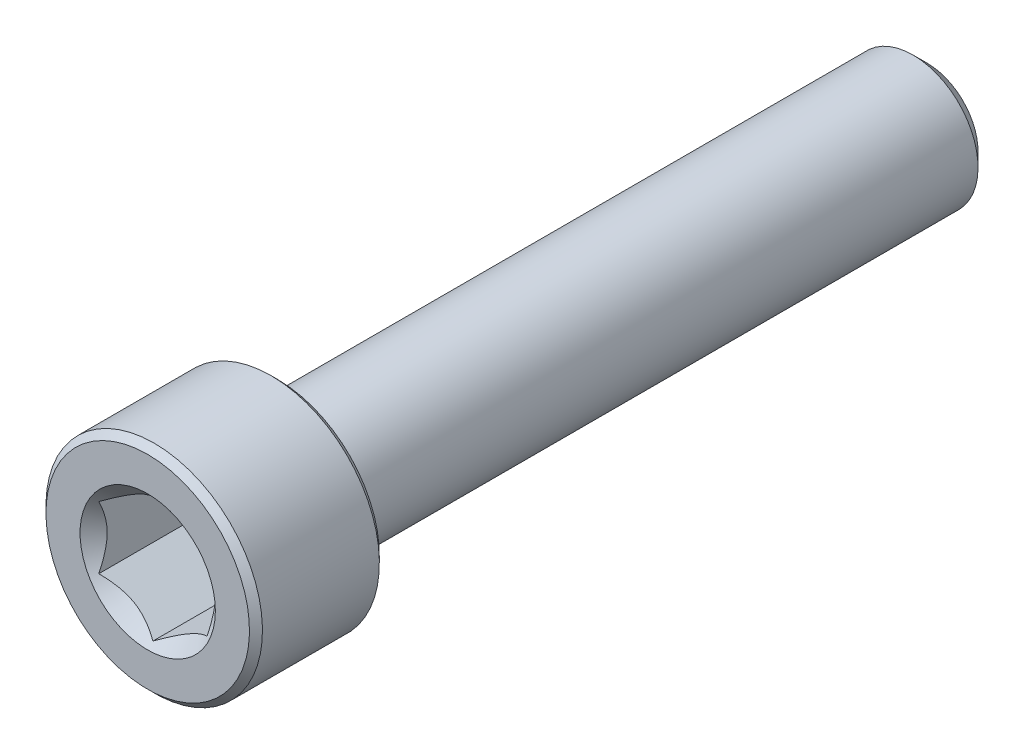
SolidWorks part; units mm, degrees
ref_plane "Front Plane" through (0, 0, 0) normal (0, 0, 1) x (1, 0, 0)
ref_plane "Top Plane" through (0, 0, 0) normal (0, 1, 0) x (1, 0, 0)
ref_plane "Right Plane" through (0, 0, 0) normal (1, 0, 0) x (0, 0, -1)
sketch "Sketch1" plane through (0, 0, 0) normal (1, 0, 0) x (0, 0, -1)
  line L0 (-18, 0) -> (18, 0) construction
  line L1 (18, 0) -> (18, 2.3505) construction
  line L2 (18, 2.3505) -> (17.3505, 3) construction
  line L3 (17.3505, 3) -> (17.25, 3) construction
  line L4 (17.25, 3) -> (-12, 3) construction
  line L5 (-12, 3) -> (-12, 5) construction
  line L6 (-12, 5) -> (-18, 5) construction
  line L7 (-18, 5) -> (-18, 0) construction
  line L8 (18, 2.3505) -> (18, 3) construction
  line L9 (17.9375, 3.1083) -> (18.4375, 2.2422) construction
  line L10 (18.4375, 2.2422) -> (18.9375, 3.1083) construction
  line L11 (18.9375, 3.1083) -> (17.9375, 3.1083) construction
  line L12 (18.4375, 3.1083) -> (18.4375, 3) construction
  line L13 (18.4375, 2.2422) -> (18.4375, 2.3505) construction
  line L14 (18.375, 2.3505) -> (18.5, 2.3505) construction
  line L15 (18, 3) -> (18.875, 3) construction
  line L16 (17.9687, 3.0541) -> (18.9063, 3.0541) construction
  line L17 (18, 0) -> (18, -3) construction
  line L18 (-12.3, 5) -> (-12, 4.7) construction
  line L19 (-17.7, 5) -> (-18, 4.7) construction
  line L20 (-12, 3) -> (-12, 0) construction
  line L21 (-12, 1.5) -> (-2, 1.5) construction
  line L22 (-2, 1.5) -> (8, 1.5) construction
  line L23 (8, 1.5) -> (18, 1.5) construction
  line L24 (-2, 1.5) -> (-2, 3) construction
  line L25 (-2, 3) -> (-2, 5) construction
  line L26 (8, 1.5) -> (8, 5) construction
  point P0 (-18, 2.5)
  point P3 (15.5, 3)
  point P4 (0, 0)
  point P18 (8, 3)
  point P22 (18.4375, 2.3505)
  point P24 (17.25, 3)
  point P25 (18.4375, 3)
  point P28 (18.4375, 3.0541)
  point P29 (15.5, -3)
  point P30 (-2, 3)
  point P31 (-15, 5)
  point P37 (-13.05, 5)
  point P38 (-17.55, 5)
  point P45 (-2, 1.5)
  point P46 (8, 1.5)
  dimension "D2" = 0.125
  dimension "D7" = 0.3
  dimension "D8" = 0.3
  dimension "D9" = 0.3
  dimension "D10" = 0.15
  dimension "D11" = 0.75
  dimension "Drive Size" = 5
  dimension "Head Diameter" = 10
  dimension "Head Height" = 6
  dimension "Thread Pitch" = 1
  dimension "Thread Size" = 6
  dimension "Length" = 30
  dimension "D12" = 0.75
  dimension "D4" = 2.5
  dimension "D3" = 45
sketch "Sketch2" plane through (0, 0, 0) normal (1, 0, 0) x (0, 0, -1)
  line L0 (-18, 0) -> (-18, 4.7)
  line L1 (-17.7, 5) -> (-12.3, 5)
  line L2 (-12, 4.7) -> (-12, 3.3)
  line L4 (17.3505, 3) -> (18, 2.3505)
  line L5 (18, 2.3505) -> (18, 0)
  line L6 (-12, 5) -> (-18, 5) construction
  line L7 (18, 0) -> (-18, 0)
  line L8 (-17.7, 5) -> (-18, 4.7) construction
  line L10 (-17.7, 5) -> (-18, 4.7)
  line L14 (-12.3, 5) -> (-12, 4.7) construction
  line L16 (-12.3, 5) -> (-12, 4.7)
  line L17 (-12, 3) -> (-12, 5) construction
  line L19 (-11.7, 3) -> (17.3505, 3)
  line L20 (17.25, 3) -> (-12, 3) construction
  arc A1 (-12, 3.3) -> (-11.7, 3) centre (-11.7, 3.3) ccw
  dimension "D3" = 0.3
revolve "Revolve1" add sketch "Sketch2" angle 360 about L7
sketch "Sketch3" plane through (0, 0, 18) normal (0, 0, 1) x (1, 0, 0)
  line L1 (2.5, -1.4434) -> (2.5, 1.4434)
  line L2 (2.5, 1.4434) -> (0, 2.8868)
  line L3 (0, 2.8868) -> (-2.5, 1.4434)
  line L4 (-2.5, 1.4434) -> (-2.5, -1.4434)
  line L5 (-2.5, -1.4434) -> (0, -2.8868)
  line L6 (0, -2.8868) -> (2.5, -1.4434)
  circle A0 centre (0, 0) radius 2.5 construction
  circle A1 centre (0, 0) radius 5 construction
  circle A2 centre (0, 0) radius 5 construction
  circle A3 centre (0, 0) radius 2.8868 construction
  point P13 (0, 0)
extrude "Cut-Extrude1" cut sketch "Sketch3" against normal offset from surface (5 mm away) 1 up to face at (0, 4.7, 12)
sketch "Sketch4" plane through (0, 0, 18) normal (0, 0, 1) x (1, 0, 0)
  circle A0 centre (0, 0) radius 3.125
  dimension "D1" = 6.25
extrude "Cut-Extrude2" cut sketch "Sketch4" against normal up to vertex (3 mm away) draft 45 up to point (0, 5, 15)
sketch "Sketch11" plane through (0, 0, 0) normal (1, 0, 0) x (0, 0, -1)
  line L0 (-18, 0) -> (18, 0) construction
  line L1 (-18, 0) -> (18, 0) construction
  line L2 (-6.375, 0) -> (-6.375, 3) construction
  line L3 (17.25, 3) -> (-12, 3) construction
  line L4 (12.375, 0) -> (12.375, 3) construction
  line L6 (18, 2.3505) -> (18, 3) construction
  point P2 (-6.375, 0)
  point P3 (12.375, 0)
  dimension "D1" = 5.625
  dimension "D2" = 5.625
sketch "Sketch6" [suppressed] plane through (0, 0, -18) normal (0, 0, -1) x (-1, 0, 0)
  circle A0 centre (0, 0) radius 3
curve "Helix/Spiral1" [suppressed] pitch 1 height 31 turns 31
sketch "Sketch10" [suppressed] plane through (0, 0, 0) normal (1, 0, 0) x (0, 0, -1)
  line L0 (-11.7, -5) -> (-11.7, 5)
  line L5 (-18, 0) -> (18, 0) construction
  line L6 (-11.7, 3) -> (-11.7, -3) construction
  point P3 (-11.7, 0)
split "Split1" [suppressed] bodies to split 106
sketch "Sketch7" [suppressed] plane through (0, 0, 0) normal (1, 0, 0) x (0, 0, -1)
  line L0 (17.9687, 3.0541) -> (18.9063, 3.0541)
  line L1 (18.9063, 3.0541) -> (18.5, 2.3505)
  line L2 (18.5, 2.3505) -> (18.375, 2.3505)
  line L3 (18.375, 2.3505) -> (17.9687, 3.0541)
sweep "Cut-Sweep1" [suppressed] cut profiles "Sketch7" path "Helix/Spiral1"
sketch "Sketch8" [suppressed] plane through (0, 0, 0) normal (1, 0, 0) x (0, 0, -1)
  line L0 (-12, 0) -> (-12, 3)
  line L1 (-11.7, -3) -> (-11.7, 3) construction
  line L2 (-12, 3) -> (-11.7, 3)
  line L4 (-11.7, 3) -> (-9.9679, 0)
  line L5 (-9.9679, 0) -> (-12, 0)
  line L6 (17.25, 3) -> (-12, 3) construction
  line L7 (-18, 0) -> (18, 0) construction
  dimension "D1" = 60
revolve "Revolve2" [suppressed] add sketch "Sketch8" angle 360 about L5
ref_plane "Plane1" [suppressed] through (0, 0, 18) normal (0, 0, 1) x (1, 0, 0)
sketch "Sketch12" [suppressed] plane through (0, 0, 18) normal (0, 0, 1) x (1, 0, 0)
  line L0 (0, 0) -> (0.1745, 4.997) construction
  line L1 (0, 0) -> (-0.1745, 4.997) construction
  line L2 (0, 4.875) -> (0, 5.125) construction
  line L3 (-0.3025, 5.125) -> (0.3025, 5.125)
  line L4 (-0.3025, 5.125) -> (-0.0897, 4.9122)
  line L5 (0.0897, 4.9122) -> (0.3025, 5.125)
  circle A0 centre (0, 0) radius 5 construction
  arc A1 (-0.0897, 4.9122) -> (0.0897, 4.9122) centre (0, 5.0019) ccw
  point P9 (0, 5.125)
  point P13 (0, 5)
  dimension "D2" = 0.125
  dimension "D1" = 4
extrude "Cut-Extrude3" [suppressed] cut sketch "Sketch12" against normal blind 4.8
pattern_circular "CirPattern1" [suppressed] count 72 over 360 about axis through (0, 0, 18) along (0, 0, -1) of bodies 118
equation "\"D2@Sketch1\" = \"Thread Pitch@Sketch1\" / 8"
equation "\"D4@Helix/Spiral1\" = \"Thread Pitch@Sketch1\""
equation "\"D7@Sketch1\" = \"Head Height@Sketch1\" * .05"
equation "\"D8@Sketch1\"=\"D7@Sketch1\""
equation "\"D9@Sketch1\"=\"D7@Sketch1\""
equation "\"D10@Sketch1\"=\"D7@Sketch1\"/2"
equation "\"D11@Sketch1\"=\"D10@Sketch1\"*5"
equation "\"D4@Sketch1\"=\"Thread Pitch@Sketch1\"*2.5"
equation "\"D12@Sketch1\"=\"Thread Pitch@Sketch1\"*.75"
equation "\"D3@Helix/Spiral1\"=\"Length@Sketch1\"+\"Thread Pitch@Sketch1\""
equation "\"D3@Sketch2\" = \"Thread Size@Sketch1\" * 0.05"
equation "\"D1@Sketch11\"=\"Length@Sketch1\"*0.1875"
equation "\"D2@Sketch11\"=\"D1@Sketch11\""
equation "\"D2@Sketch12\"=\"Head Diameter@Sketch1\"*.0125"
equation "\"D1@Cut-Extrude3\"=\"Head Height@Sketch1\"*.8"
equation "\"D1@CirPattern1\"=\"D3@CirPattern1\"/(1.25*\"D1@Sketch12\")"
equation "\"D1@Sketch4\"=\"Drive Size@Sketch1\"*1.25"
